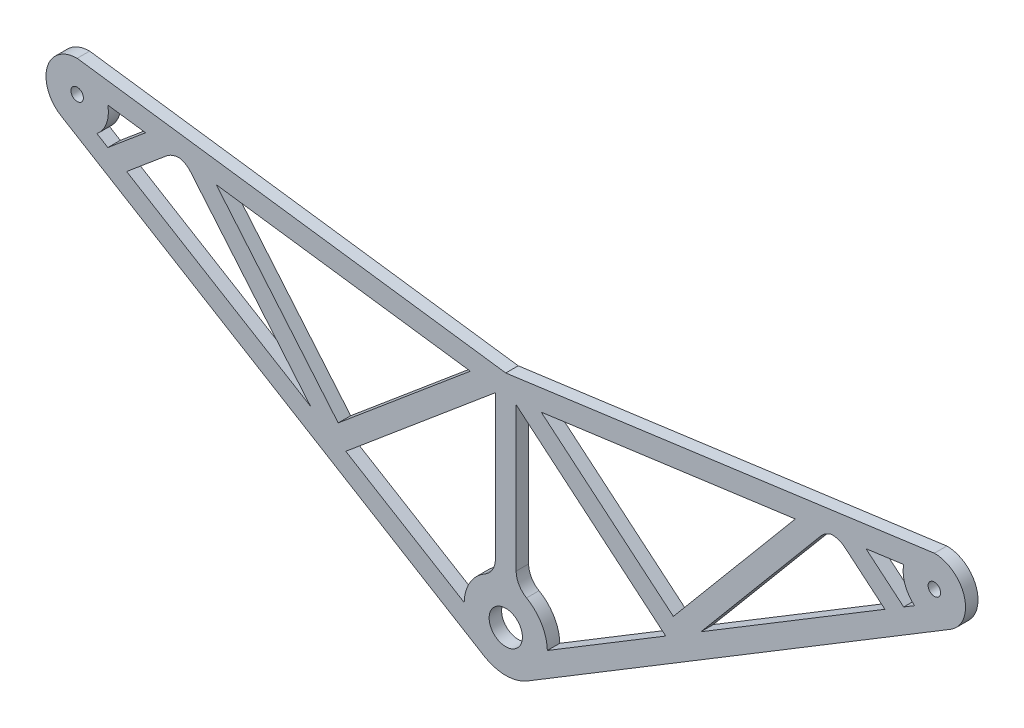
SolidWorks part; units mm, degrees
ref_plane "前视基准面" through (0, 0, 0) normal (0, 0, 1) x (1, 0, 0)
ref_plane "上视基准面" through (0, 0, 0) normal (0, 1, 0) x (1, 0, 0)
ref_plane "右视基准面" through (0, 0, 0) normal (1, 0, 0) x (0, 0, -1)
sketch "草图1" plane through (0, 0, 0) normal (0, 0, 1) x (1, 0, 0)
  line L0 (0, 53) -> (0, -10) construction
  line L1 (0, 0) -> (103.057, 59.5) construction
  line L2 (0, 53) -> (-103.057, 67)
  line L3 (0, 0) -> (-103.057, 59.5) construction
  line L4 (0, 53) -> (103.057, 67)
  line L5 (-106.9426, 53.085) -> (-5.1808, -8.5533)
  line L6 (5.1808, -8.5533) -> (106.9426, 53.085)
  line L7 (0, 53) -> (-40.6004, 18.9323) construction
  line L8 (0, 53) -> (40.6004, 18.9323) construction
  line L9 (-40.6004, 18.9323) -> (-78.0878, 63.608) construction
  line L10 (40.6004, 18.9323) -> (78.0878, 63.608) construction
  line L11 (-78.0878, 63.608) -> (-93.1067, 51.0056) construction
  line L12 (78.0878, 63.608) -> (93.1067, 51.0056) construction
  line L13 (-8.523, 49.1119) -> (-69.6256, 57.4125)
  line L14 (46.9198, 22.5742) -> (91.1632, 49.3729)
  line L15 (-98.3041, 53.6983) -> (-95.6807, 52.1092)
  line L16 (9.9978, 0.2101) -> (38.4702, 17.4562)
  line L17 (-8.523, 49.1119) -> (-40.2922, 22.4543)
  line L18 (-40.2922, 22.4543) -> (-69.6256, 57.4125)
  line L19 (-86.6107, 59.7199) -> (-95.6807, 52.1092)
  line L20 (-2.5, 47.6387) -> (-38.4702, 17.4562)
  line L21 (-46.9198, 22.5742) -> (-76.9924, 58.4133)
  line L22 (-79.916, 58.8104) -> (-91.1632, 49.3729)
  line L23 (2.5, 47.6387) -> (38.4702, 17.4562)
  line L24 (46.9198, 22.5742) -> (76.9924, 58.4133)
  line L25 (79.916, 58.8104) -> (91.1632, 49.3729)
  line L26 (8.523, 49.1119) -> (40.2922, 22.4543)
  line L27 (40.2922, 22.4543) -> (69.6256, 57.4125)
  line L28 (86.6107, 59.7199) -> (95.6807, 52.1092)
  line L29 (-38.4702, 17.4562) -> (-9.9978, 0.2101)
  line L30 (-2.5, 47.6387) -> (-2.5, 9.6825)
  line L31 (2.5, 47.6387) -> (2.5, 9.6825)
  line L32 (77.7796, 67.1301) -> (94.7136, 52.9207) construction
  line L33 (-1.607, 54.9151) -> (-40.2922, 22.4543) construction
  line L34 (1.607, 54.9151) -> (40.2922, 22.4543) construction
  line L35 (1.607, 51.0849) -> (-40.9085, 15.4102) construction
  line L36 (-1.607, 51.0849) -> (40.9085, 15.4102) construction
  line L37 (-2.5, 53) -> (-2.5, -10) construction
  line L38 (2.5, 53) -> (2.5, -10) construction
  line L39 (-40.2922, 22.4543) -> (-77.7796, 67.1301) construction
  line L40 (-77.7796, 67.1301) -> (-94.7136, 52.9207) construction
  line L41 (-40.9085, 15.4102) -> (-78.3959, 60.0859) construction
  line L42 (-78.3959, 60.0859) -> (-91.4997, 49.0905) construction
  line L43 (40.9085, 15.4102) -> (78.3959, 60.0859) construction
  line L44 (2.5, -9.6825) -> (2.5, -10)
  line L45 (40.2922, 22.4543) -> (77.7796, 67.1301) construction
  line L46 (78.3959, 60.0859) -> (91.4997, 49.0905) construction
  line L47 (-2.5, -9.6825) -> (-2.5, -10)
  line L49 (-104.3522, 57.3617) -> (-2.5904, -4.2767) construction
  line L50 (2.5904, -4.2767) -> (104.3522, 57.3617) construction
  line L51 (86.6107, 59.7199) -> (95.6994, 60.9546)
  line L52 (95.6807, 52.1092) -> (98.3041, 53.6983)
  line L53 (76.9924, 58.4133) -> (79.916, 58.8104)
  line L54 (8.523, 49.1119) -> (69.6256, 57.4125)
  line L55 (-76.9924, 58.4133) -> (-79.916, 58.8104)
  line L56 (-86.6107, 59.7199) -> (-95.6994, 60.9546)
  line L57 (-91.1632, 49.3729) -> (-46.9198, 22.5742)
  arc A0 (-2.5, 9.6825) -> (-9.9978, 0.2101) centre (0, 0) ccw
  arc A1 (-98.3041, 53.6983) -> (-95.6994, 60.9546) centre (-103.057, 59.5) ccw
  arc A2 (106.9426, 53.085) -> (101.0562, 66.7282) centre (103.057, 59.5) ccw
  circle A3 centre (0, 0) radius 4
  circle A4 centre (-103.057, 59.5) radius 1.5
  circle A5 centre (103.057, 59.5) radius 1.5
  arc A6 (-5.1808, -8.5533) -> (5.1808, -8.5533) centre (0, 0) ccw
  arc A7 (9.9978, 0.2101) -> (2.5, 9.6825) centre (0, 0) ccw
  arc A8 (95.6994, 60.9546) -> (98.3041, 53.6983) centre (103.057, 59.5) ccw
  arc A9 (-101.0562, 66.7282) -> (-106.9426, 53.085) centre (-103.057, 59.5) ccw
  point P5 (0, 53)
  dimension "D1" = 8
  dimension "D2" = 20
  dimension "D3" = 3
  dimension "D4" = 15
  dimension "D5" = 3
  dimension "D6" = 15
  dimension "D7" = 60
  dimension "D8" = 60
  dimension "D9" = 119
  dimension "D10" = 119
  dimension "D11" = 53
  dimension "D12" = 53
  dimension "D13" = 53
  dimension "D23" = 5
  dimension "D15" = 5
  dimension "D24" = 5
  dimension "D25" = 5
  dimension "D26" = 50
  dimension "D27" = 50
  dimension "D14" = 2.5
  dimension "D16" = 5
  dimension "D17" = 5
  dimension "D18" = 2.5
  dimension "D19" = 2.5
  dimension "D20" = 2.5
  dimension "D21" = 2.5
  dimension "D22" = 2.5
extrude "凸台-拉伸1" add sketch "草图1" along normal blind 3 contours L2 A9 L5 A6 L6 A2 L4 L51 A8 L52 L28 L16 A7 L31 L23 L15 A1 L56 L19 L30 A0 L29 L20 L26 L54 L27 L24 L53 L25 L14 L17 L18 L13 L57 L22 L55 L21 A3 region at (0, 38.2308, 0)
fillet "圆角1" radius 5 2 edges at (76.9924, 58.4133, 1.5) (79.916, 58.8104, 1.5)
fillet "圆角2" radius 5 2 edges at (-79.916, 58.8104, 1.5) (-76.9924, 58.4133, 1.5)
fillet "圆角3" radius 5 2 edges at (2.5, 9.6825, 1.5) (-2.5, 9.6825, 1.5)
